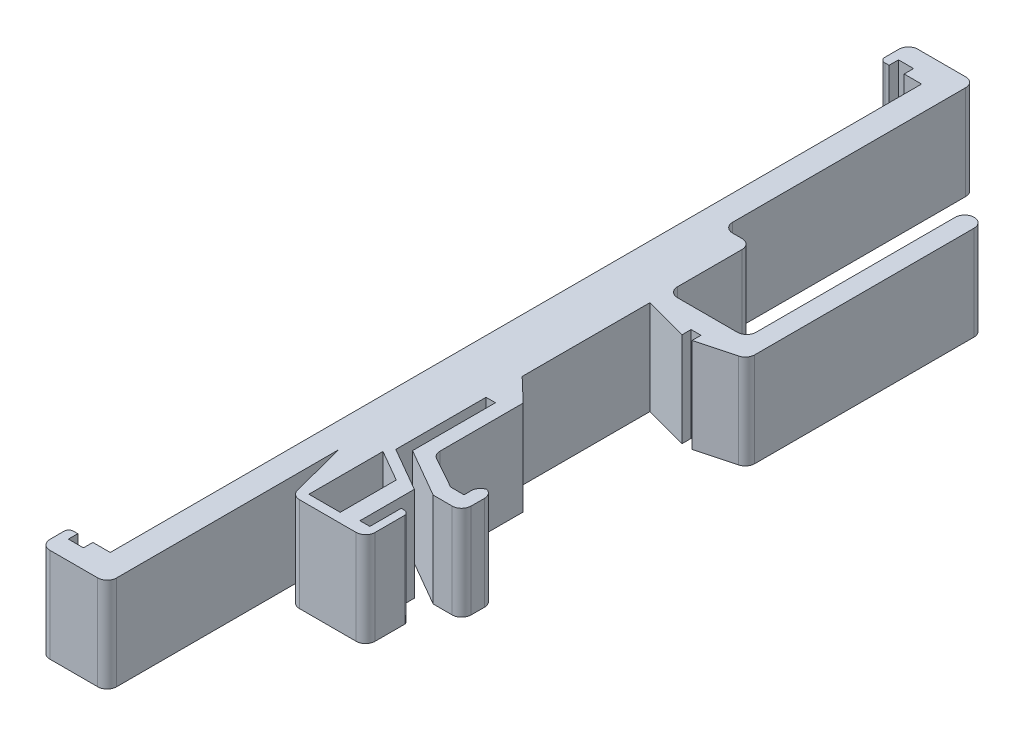
SolidWorks part; units mm, degrees
ref_plane "Front Plane" through (0, 0, 0) normal (0, 0, 1) x (1, 0, 0)
ref_plane "Top Plane" through (0, 0, 0) normal (0, 1, 0) x (1, 0, 0)
ref_plane "Right Plane" through (0, 0, 0) normal (1, 0, 0) x (0, 0, -1)
ref_plane "Plane4" through (0, -10, 0) normal (0, -1, 0) x (1, 0, 0)
sketch "Sketch1" plane through (0, -10, 0) normal (0, -1, 0) x (1, 0, 0)
  line L0 (2.8043, 17.5335) -> (5.3043, 19.9248)
  line L1 (5.3043, 19.9248) -> (5.3043, 29.3242)
  line L2 (5.3043, 29.3242) -> (9.1697, 31.4805)
  line L3 (9.1697, 31.4805) -> (10.5952, 31.4805)
  line L4 (10.5952, 31.4805) -> (10.5778, 29.7304)
  line L5 (10.5778, 29.7304) -> (12.0126, 29.7304)
  line L6 (12.0126, 29.7304) -> (11.9813, 33.1415)
  line L7 (11.9813, 33.1415) -> (8.9813, 33.1415)
  line L8 (8.9813, 33.1415) -> (3.8043, 30.1526)
  line L9 (3.8043, 30.1526) -> (3.8043, 21.3596)
  line L10 (3.8043, 21.3596) -> (2.8043, 21.3596)
  line L11 (2.8043, 21.3596) -> (2.8043, 30.9248)
  line L12 (2.8043, 30.9248) -> (7.4523, 33.6083)
  line L13 (7.4523, 33.6083) -> (7.4523, 39.3759)
  line L14 (7.4523, 39.3759) -> (8.5023, 39.3759)
  line L15 (8.5023, 39.3759) -> (8.5023, 36.0507)
  line L16 (8.5023, 36.0507) -> (9.3284, 36.0507)
  line L17 (9.3284, 36.0507) -> (9.3284, 40.6507)
  line L18 (9.3284, 40.6507) -> (1.5382, 40.6507)
  line L19 (1.5382, 40.6507) -> (-0.1957, 33.955)
  line L20 (-0.1957, 33.955) -> (-0.1957, 58.5217)
  line L21 (-0.1957, 58.5217) -> (-7.2696, 58.5217)
  line L22 (-7.2696, 58.5217) -> (-7.2696, 55.5217)
  line L23 (-7.2696, 55.5217) -> (-6.313, 55.5217)
  line L24 (-6.313, 55.5217) -> (-6.313, 56.5217)
  line L25 (-6.313, 56.5217) -> (-4.713, 56.5217)
  line L26 (-4.713, 56.5217) -> (-4.713, 55.5217)
  line L27 (-4.713, 55.5217) -> (-2.8696, 55.5217)
  line L28 (-2.8696, 55.5217) -> (-2.8696, 4.3872)
  line L29 (-2.8696, 4.3872) -> (-2.8696, -9.4348)
  line L32 (-2.8696, -9.4348) -> (-2.8696, -30.4783)
  line L33 (-2.8696, -30.4783) -> (-4.713, -30.4783)
  line L34 (-4.713, -30.4783) -> (-4.713, -31.4783)
  line L35 (-4.713, -31.4783) -> (-6.313, -31.4783)
  line L36 (-6.313, -31.4783) -> (-6.313, -30.4783)
  line L37 (-6.313, -30.4783) -> (-7.2696, -30.4783)
  line L38 (-7.2696, -30.4783) -> (-7.2696, -33.4783)
  line L39 (-7.2696, -33.4783) -> (-0.1957, -33.4783)
  line L40 (-0.1957, -33.4783) -> (-0.1957, -6.7777)
  line L41 (-0.1957, -6.7777) -> (2.8043, -6.7777)
  line L42 (2.8043, -6.7777) -> (2.8043, 2.074)
  line L43 (2.8043, 2.074) -> (11.1462, 2.074)
  line L44 (11.1462, 2.074) -> (11.1462, -21.0349)
  line L45 (11.1462, -21.0349) -> (13.1462, -21.0349)
  line L46 (13.1462, -21.0349) -> (13.1462, 3.987)
  line L47 (13.1462, 3.987) -> (8.5023, 5.2324)
  line L48 (8.5023, 5.2324) -> (8.5023, 4.2759)
  line L49 (8.5023, 4.2759) -> (7.4523, 4.2759)
  line L50 (7.4523, 4.2759) -> (7.4523, 5.2324)
  line L51 (7.4523, 5.2324) -> (2.8043, 3.987)
  line L52 (2.8043, 3.987) -> (2.8043, 17.5335)
  line L53 (2.3142, 31.7965) -> (2.3142, 39.6507)
  line L54 (2.3142, 39.6507) -> (5.6384, 39.6507)
  line L55 (5.6384, 39.6507) -> (5.6384, 33.7157)
  line L56 (5.6384, 33.7157) -> (2.3142, 31.7965)
  point P57 (7.237, 30.4024)
  dimension "D1" = 88
  dimension "D2" = 2
  dimension "D3" = 2
  dimension "D4" = 1
  dimension "D5" = 1
  dimension "D6" = 1.6
  dimension "D7" = 1.05
  dimension "D8" = 35.1
  dimension "D9" = 1
  dimension "D10" = 4.6
  dimension "D11" = 3
  dimension "D12" = 1.5
  dimension "D13" = 1
  dimension "D14" = 1.5
  dimension "D15" = 1
  dimension "D16" = 3
  dimension "D17" = 2
  dimension "D18" = 2.2019
extrude "Boss-Extrude1" add sketch "Sketch1" against normal blind 10
fillet "Fillet1" radius 1 17 edges at (11.9813, -5, 33.1415) (10.5778, -5, 29.7304) (12.0126, -5, 29.7304) (13.1462, -5, -21.0349) (2.8043, -5, 2.074) (-0.1957, -5, -6.7777) (2.8043, -5, -6.7777) (11.1462, -5, -21.0349) (13.1462, -5, 3.987) (11.1462, -5, 2.074) (-0.1957, -5, -33.4783) (-7.2696, -5, -33.4783) (-7.2696, -5, 58.5217) (-0.1957, -5, 58.5217) (5.3043, -5, 29.3242) (9.3284, -5, 40.6507) (1.5382, -5, 40.6507)
fillet "Fillet2" radius 0.5 3 edges at (9.3284, -5, 36.0507) (-7.2696, -5, -30.4783) (-7.2696, -5, 55.5217)
